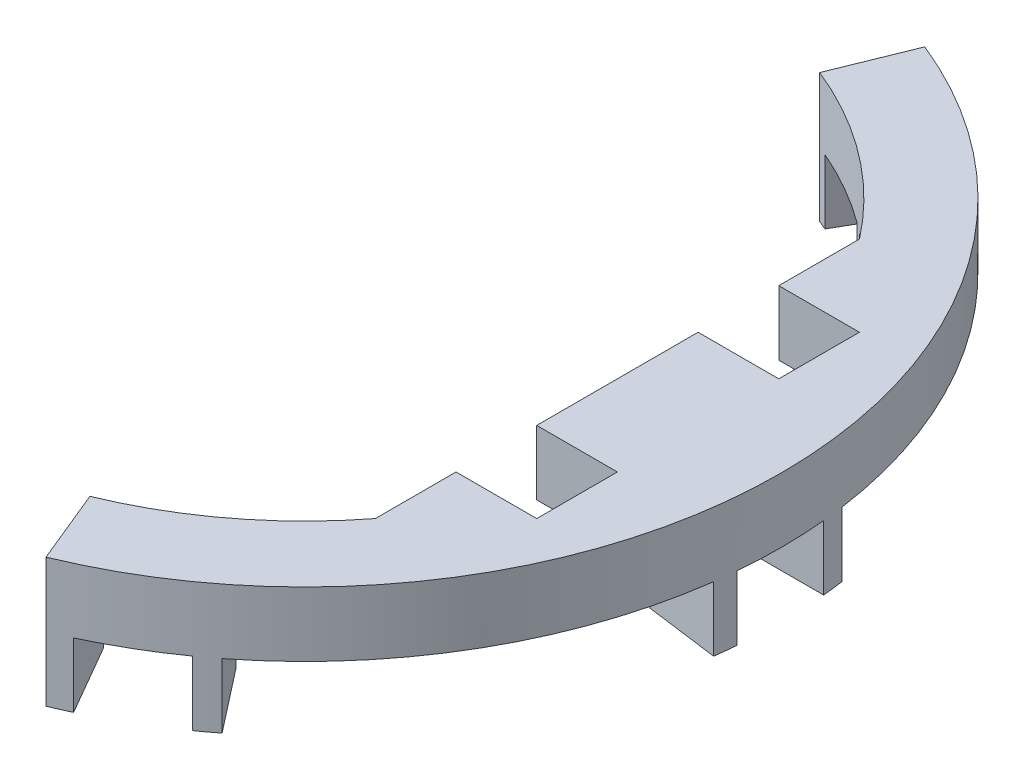
SolidWorks part; units mm, degrees
ref_plane "Front Plane" through (0, 0, 0) normal (0, 0, 1) x (1, 0, 0)
ref_plane "Top Plane" through (0, 0, 0) normal (0, 1, 0) x (1, 0, 0)
ref_plane "Right Plane" through (0, 0, 0) normal (1, 0, 0) x (0, 0, -1)
sketch "Sketch1" plane through (0, 0, 0) normal (0, 1, 0) x (1, 0, 0)
  line L2 (48.5304, 6.7678) -> (58.4345, 8.149)
  line L3 (18.4041, 45.4124) -> (22.1601, 54.6803)
  line L5 (29.9044, 38.8166) -> (36.0074, 46.7383)
  line L6 (48.5683, -6.4897) -> (58.4802, -7.8142)
  line L7 (58.7366, 5.569) -> (48.6825, 5.569)
  line L8 (58.7676, -5.231) -> (48.72, -5.231)
  line L9 (24.5454, 53.6519) -> (19.5184, 44.9448)
  line L10 (33.914, 48.2788) -> (28.8902, 39.5772)
  line L12 (30.1263, -38.6446) -> (36.2745, -46.5313)
  line L13 (18.6639, -45.3063) -> (22.4729, -54.5525)
  line L14 (34.1911, -48.0829) -> (29.1641, -39.3758)
  line L15 (24.8536, -53.5098) -> (19.8298, -44.8083)
  line L32 (-18.4041, -45.4124) -> (-22.1601, -54.6803) [skipped]
  line L33 (-29.9044, -38.8166) -> (-36.0074, -46.7383) [skipped]
  line L34 (-24.5454, -53.6519) -> (-19.5184, -44.9448) [skipped]
  line L35 (-33.914, -48.2788) -> (-28.8902, -39.5772) [skipped]
  line L37 (-48.5304, -6.7678) -> (-58.4345, -8.149) [skipped]
  line L38 (-48.5683, 6.4897) -> (-58.4802, 7.8142) [skipped]
  line L39 (-58.7366, -5.569) -> (-48.6825, -5.569) [skipped]
  line L40 (-58.7676, 5.231) -> (-48.72, 5.231) [skipped]
  line L42 (-30.1263, 38.6446) -> (-36.2745, 46.5313) [skipped]
  line L43 (-18.6639, 45.3063) -> (-22.4729, 54.5525) [skipped]
  line L44 (-34.1911, 48.0829) -> (-29.1641, 39.3758) [skipped]
  line L45 (-24.8536, 53.5098) -> (-19.8298, 44.8083) [skipped]
  arc A0 (22.4729, -54.5525) -> (24.8536, -53.5098) centre (0, 0) ccw
  arc A1 (18.6639, -45.3063) -> (19.8298, -44.8083) centre (0, 0) ccw
  arc A2 (36.0074, 46.7383) -> (33.914, 48.2788) centre (0, 0) ccw
  arc A3 (29.9044, 38.8166) -> (28.8902, 39.5772) centre (0, 0) ccw
  arc A4 (58.4802, -7.8142) -> (58.7676, -5.231) centre (0, 0) ccw
  arc A5 (48.5683, -6.4897) -> (48.72, -5.231) centre (0, 0) ccw
  arc A6 (24.5454, 53.6519) -> (22.1601, 54.6803) centre (0, 0) ccw
  arc A7 (19.5184, 44.9448) -> (18.4041, 45.4124) centre (0, 0) ccw
  arc A8 (58.7366, 5.569) -> (58.4345, 8.149) centre (0, 0) ccw
  arc A9 (48.6825, 5.569) -> (48.5304, 6.7678) centre (0, 0) ccw
  arc A10 (29.1641, -39.3758) -> (30.1263, -38.6446) centre (0, 0) ccw
  arc A11 (34.1911, -48.0829) -> (36.2745, -46.5313) centre (0, 0) ccw
  dimension "D1" = 118
  dimension "D10" = 98
  dimension "D5" = 6
extrude "Boss-Extrude1" add sketch "Sketch1" along normal blind 8
sketch "Sketch2" plane through (0, 8, 0) normal (0, 1, 0) x (1, 0, 0)
  line L0 (22.1601, 54.6803) -> (18.4041, 45.4124)
  line L1 (18.6639, -45.3063) -> (22.4729, -54.5525)
  arc A0 (22.4729, -54.5525) -> (22.1601, 54.6803) centre (0, 0) ccw
  arc A1 (18.6639, -45.3063) -> (18.4041, 45.4124) centre (0, 0) ccw
extrude "Boss-Extrude2" add sketch "Sketch2" along normal blind 8
sketch "Sketch3" plane through (0, 8, 0) normal (0, -1, 0) x (1, 0, 0)
  line L0 (38.7427, -30) -> (38.7427, 30)
  arc A0 (38.7427, -30) -> (38.7427, 30) centre (0, 0) ccw
  dimension "D1" = 98
  dimension "D2" = 60
extrude "Boss-Extrude3" add sketch "Sketch3" against normal blind 8
sketch "Sketch7" plane through (0, 16, 0) normal (0, 1, 0) x (1, 0, 0)
  line L0 (38.7427, -30) -> (38.7427, 30) construction
  line L1 (38.7427, 20) -> (48.7427, 20)
  line L2 (38.7427, 20) -> (38.7427, 10)
  line L3 (38.7427, 10) -> (48.7427, 10)
  line L4 (48.7427, 20) -> (48.7427, 10)
  line L6 (38.7427, -10) -> (48.7427, -10)
  line L7 (38.7427, -10) -> (38.7427, -20)
  line L8 (38.7427, -20) -> (48.7427, -20)
  line L9 (48.7427, -10) -> (48.7427, -20)
  dimension "D1" = 10
  dimension "D2" = 10
  dimension "D3" = 10
  dimension "D4" = 10
  dimension "D5" = 10
  dimension "D6" = 10
extrude "Cut-Extrude1" cut sketch "Sketch7" against normal blind 70
